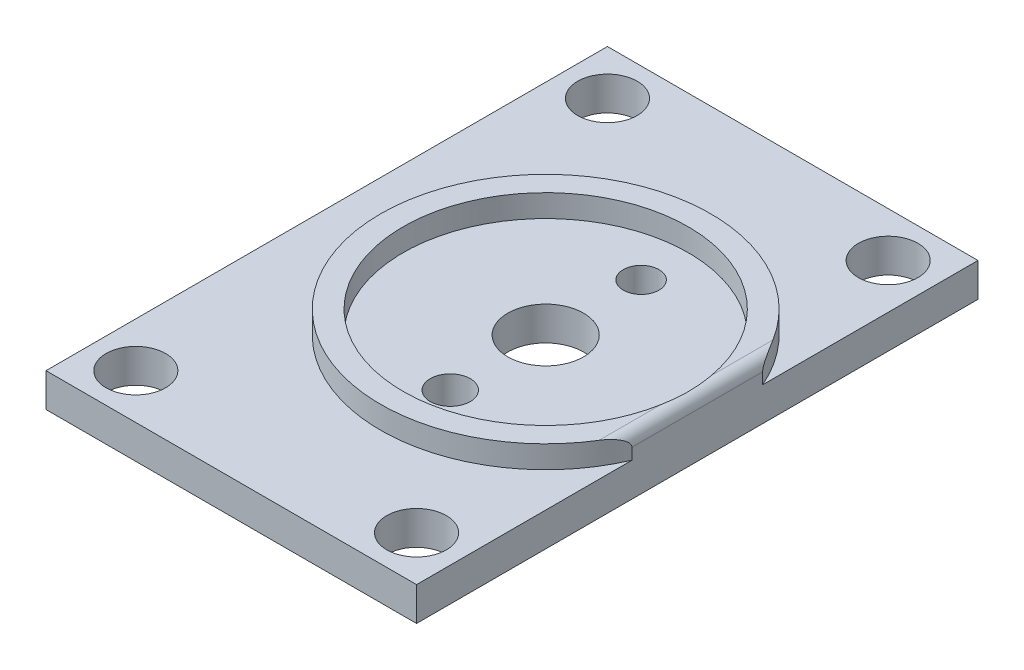
SolidWorks part; units mm, degrees
ref_plane "Front Plane" through (0, 0, 0) normal (0, 0, 1) x (1, 0, 0)
ref_plane "Top Plane" through (0, 0, 0) normal (0, 1, 0) x (1, 0, 0)
ref_plane "Right Plane" through (0, 0, 0) normal (1, 0, 0) x (0, 0, -1)
sketch "Sketch1" plane through (0, 0, 0) normal (0, 1, 0) x (1, 0, 0)
  line L1 (-10.223, 36.3848) -> (14.777, 36.3848)
  line L2 (-10.223, 36.3848) -> (-10.223, -13.6152)
  line L3 (-10.223, -13.6152) -> (14.777, -13.6152)
  line L4 (14.777, 36.3848) -> (14.777, -13.6152)
  circle A0 centre (1.277, 11.3848) radius 3.375
  dimension "D3" = 6.75
  dimension "D1" = 50
  dimension "D2" = 25
  dimension "D4" = 13.5
  dimension "D5" = 25
extrude "Boss-Extrude1" add sketch "Sketch1" along normal blind 3
sketch "Sketch2" plane through (-10.223, 0, 0) normal (-1, 0, 0) x (0, 0, 1)
  line L0 (18.15, 0) -> (-18.15, 0) construction
  line L1 (-36.3848, 3) -> (13.6152, 3)
  line L2 (-36.3848, 3) -> (-36.3848, 0)
  line L3 (-36.3848, 0) -> (13.6152, 0)
  line L4 (13.6152, 3) -> (13.6152, 0)
  line L5 (13.6152, 3) -> (13.6152, 0) construction
extrude "Boss-Extrude2" add sketch "Sketch2" along normal blind 8
sketch "Sketch3" plane through (0, 0, 0) normal (0, -1, 0) x (1, 0, 0)
  line L0 (-18.223, 13.6152) -> (14.777, 13.6152) construction
  line L1 (-18.223, -36.3848) -> (-10.223, -36.3848)
  line L2 (-18.223, -36.3848) -> (-18.223, 13.6152)
  line L3 (-18.223, 13.6152) -> (-10.223, 13.6152)
  line L4 (-10.223, -36.3848) -> (-10.223, 13.6152)
  dimension "D1" = 8
extrude "Boss-Extrude3" add sketch "Sketch3" along normal blind 42
sketch "Sketch4" plane through (0, 3, 0) normal (0, 1, 0) x (1, 0, 0)
  line L0 (-18.223, -13.6152) -> (-18.223, 36.3848) construction
  line L1 (14.777, 36.3848) -> (-18.223, 36.3848) construction
  line L2 (-18.223, -13.6152) -> (14.777, -13.6152) construction
  circle A0 centre (-14.223, 32.3848) radius 2.65
  circle A1 centre (-14.223, -9.6152) radius 2.65
  dimension "D2" = 5.3
  dimension "D4" = 5.3
  dimension "D5" = 4
  dimension "D6" = 4
  dimension "D1" = 4
  dimension "D3" = 4
extrude "Cut-Extrude1" cut sketch "Sketch4" against normal blind 3.3
ref_plane "Plane1" through (0, -19.5, 0) normal (0, 1, 0) x (1, 0, 0)
mirror "Mirror1" about plane through (0, -19.5, 0) normal (0, 1, 0) of "Cut-Extrude1"
sketch "Sketch5" plane through (-18.223, 0, 0) normal (-1, 0, 0) x (0, 0, 1)
  line L0 (18.15, 0) -> (-18.15, 0) construction
  line L1 (-6.9841, -24.1818) -> (-6.6547, -18.3888) construction
  line L2 (-6.6547, -18.3888) -> (-11.5069, -15.207) construction
  line L3 (-11.5069, -15.207) -> (-16.6885, -17.8182) construction
  line L4 (-16.6885, -17.8182) -> (-17.0179, -23.6112) construction
  line L5 (-17.0179, -23.6112) -> (-12.1657, -26.793) construction
  line L6 (-12.1657, -26.793) -> (-6.9841, -24.1818) construction
  circle A0 centre (-11.8363, -21) radius 5.025 construction
  circle A1 centre (-11.8363, -21) radius 5.8024
  dimension "D1" = 21
  dimension "D2" = 10.05
extrude "Cut-Extrude2" cut sketch "Sketch5" against normal blind 9
fillet "Fillet2" radius 1 1 edges at (-10.223, -21, -6.0339)
ref_plane "Plane2" through (-1.723, 0, 0) normal (-1, 0, 0) x (0, 0, 1)
mirror "Mirror2" about plane through (-1.723, 0, 0) normal (-1, 0, 0) of "Cut-Extrude1"
sketch "Sketch6" plane through (0, 3, 0) normal (0, 1, 0) x (1, 0, 0)
  line L0 (1.277, 14.7598) -> (1.277, 8.0098) construction
  line L1 (14.777, -13.6152) -> (14.777, 36.3848) construction
  line L2 (14.777, 17.202) -> (14.777, 5.5675)
  circle A0 centre (1.277, 11.3848) radius 3.375 construction
  circle A1 centre (1.277, 11.3848) radius 3.1
  circle A2 centre (1.277, 11.3848) radius 12.7
  arc A3 (14.777, 17.202) -> (14.777, 5.5675) centre (1.277, 11.3848) ccw
  line M9 (14.777, -13.6152) -> (14.777, 36.3848)
  dimension "D1" = 25.4
  dimension "D2" = 2
extrude "Boss-Extrude4" add sketch "Sketch6" along normal blind 2 contours A3 A2 M9 region at (14.3696, 3, -11.3848)
fillet "Fillet4" radius 1 1 edges at (14.777, 5, -11.3848)
sketch "Sketch8" plane through (0, 3, 0) normal (0, 1, 0) x (1, 0, 0)
  line L0 (4.652, 11.3848) -> (-2.098, 11.3848) construction
  circle A0 centre (1.277, 11.3848) radius 3.375 construction
  circle A1 centre (1.277, 19.8848) radius 1.5898
  circle A2 centre (1.277, 2.8848) radius 1.7774
  point P9 (1.277, 11.3848)
  dimension "D1" = 8.5
  dimension "D2" = 8.5
extrude "Cut-Extrude3" cut sketch "Sketch8" against normal blind 10
sketch "Sketch9" plane through (0, 0, 13.6152) normal (0, 0, 1) x (1, 0, 0)
  line L0 (-18.223, -42) -> (-18.223, 3) construction
  line L1 (-18.223, 0) -> (-10.223, 0)
  line L2 (-18.223, 0) -> (-18.223, -42)
  line L3 (-18.223, -42) -> (-10.223, -42)
  line L4 (-10.223, 0) -> (-10.223, -42)
extrude "Cut-Extrude4" cut sketch "Sketch9" against normal through all
